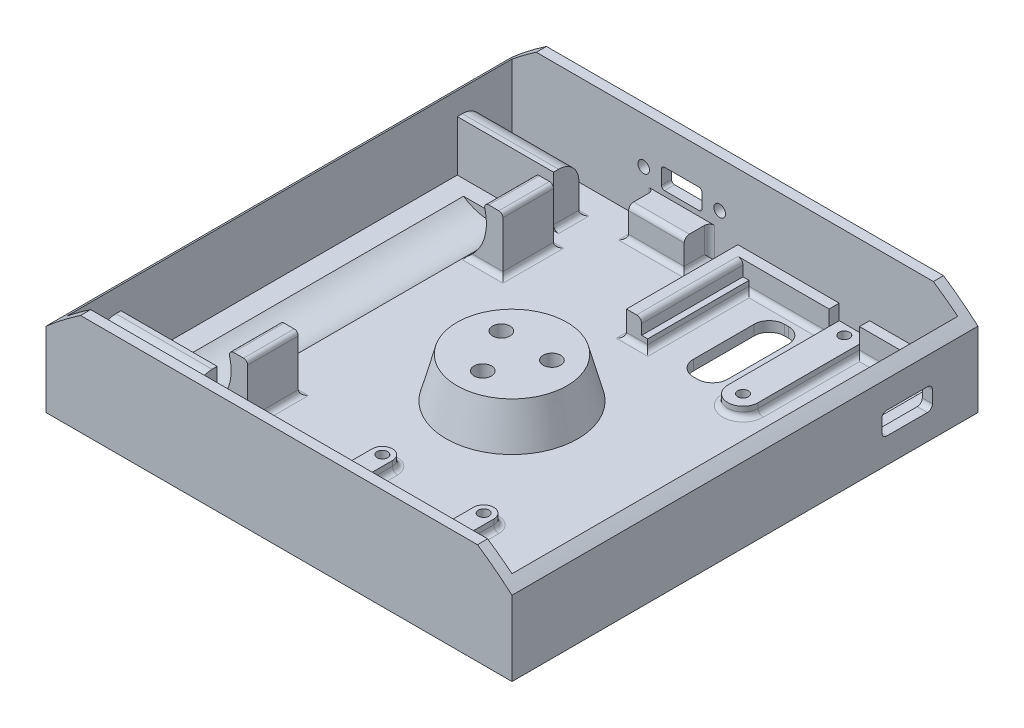
SolidWorks part; units mm, degrees
ref_plane "Front Plane" through (0, 0, 0) normal (0, 0, 1) x (1, 0, 0)
ref_plane "Top Plane" through (0, 0, 0) normal (0, 1, 0) x (1, 0, 0)
ref_plane "Right Plane" through (0, 0, 0) normal (1, 0, 0) x (0, 0, -1)
sketch "Sketch1" plane through (0, 0, 0) normal (0, 1, 0) x (1, 0, 0)
  line L1 (-46, 46) -> (46, 46)
  line L2 (-46, 46) -> (-46, -46)
  line L3 (-46, -46) -> (46, -46)
  line L4 (46, 46) -> (46, -46)
  line L5 (-46, 46) -> (46, -46) construction
  line L6 (-46, -46) -> (46, 46) construction
  point P0 (0, 0)
  dimension "D1" = 92
  dimension "D2" = 92
extrude "Boss-Extrude1" add sketch "Sketch1" along normal blind 2
sketch "Sketch7" plane through (0, 2, 0) normal (0, 1, 0) x (1, 0, 0)
  circle A0 centre (0, 0) radius 13
  dimension "D1" = 26
extrude "Boss-Extrude2" add sketch "Sketch7" along normal blind 8 draft 15
sketch "Sketch4" plane through (0, 2, 0) normal (0, 1, 0) x (1, 0, 0)
  circle A3 centre (0, -5.77) radius 1.725
  circle A4 centre (-4.997, 2.885) radius 1.725
  circle A5 centre (4.997, 2.885) radius 1.725
  point P10 (0, 0)
  dimension "D2" = 3.45
  dimension "D1" = 5.77
  dimension "D3" = 3
extrude "Cut-Extrude3" cut sketch "Sketch4" against normal through all both and the other way through all
sketch "Sketch6" plane through (0, 2, 0) normal (0, 1, 0) x (1, 0, 0)
  circle A3 centre (0, -5.77) radius 3.5
  circle A4 centre (4.997, 2.885) radius 3.5
  circle A5 centre (-4.997, 2.885) radius 3.5
  dimension "D1" = 7
  dimension "D2" = 7
  dimension "D3" = 7
extrude "Cut-Extrude4" cut sketch "Sketch6" against normal through all from offset 1
sketch "Sketch8" plane through (0, 2, 0) normal (0, 1, 0) x (1, 0, 0)
  line L0 (-46, 0) -> (46, 0) construction
  line L1 (-46, 46) -> (-46, -46) construction
  line L2 (46, -46) -> (46, 46) construction
  line L3 (-44, -33.2) -> (-25, -33.2)
  line L4 (-44, 38.2) -> (-25, 38.2)
  line L5 (-44, 38.2) -> (-44, 33.2)
  line L6 (-44, 33.2) -> (-25, 33.2)
  line L7 (-25, 38.2) -> (-25, 33.2)
  line L8 (-44, 38.2) -> (-25, 33.2) construction
  line L9 (-44, 33.2) -> (-25, 38.2) construction
  line L10 (-25, -38.2) -> (-25, -33.2)
  line L11 (-44, -38.2) -> (-44, -33.2)
  line L12 (-44, -38.2) -> (-25, -38.2)
  circle A0 centre (0, 0) radius 25 construction
  point P9 (-34.5, 35.7)
  dimension "D1" = 50
  dimension "D2" = 19
  dimension "D3" = 25
  dimension "D4" = 5
  dimension "D5" = 33.2
extrude "Boss-Extrude3" add sketch "Sketch8" along normal blind 10
fillet "Fillet1" radius 4 2 edges at (-34.5, 12, -38.2) (-34.5, 12, 38.2)
sketch "Sketch12" plane through (0, 2, 0) normal (0, 1, 0) x (1, 0, 0)
  line L0 (-46, 0) -> (46, 0) construction
  line L5 (-46, 46) -> (-46, -46) construction
  line L6 (46, -46) -> (46, 46) construction
  line L12 (-25, 33.2) -> (-25, 38.2) construction
  line L13 (-29, 30.2) -> (-22, 30.2)
  line L14 (-29, 30.2) -> (-29, 20.2)
  line L15 (-29, 20.2) -> (-22, 20.2)
  line L16 (-22, 30.2) -> (-22, 20.2)
  line L17 (-44, 33.2) -> (-25, 33.2) construction
  line L18 (-29, -20.2) -> (-22, -20.2)
  line L19 (-22, -30.2) -> (-22, -20.2)
  line L20 (-29, -30.2) -> (-29, -20.2)
  line L21 (-29, -30.2) -> (-22, -30.2)
  dimension "D1" = 10
  dimension "D2" = 7
  dimension "D3" = 4
  dimension "D4" = 3
extrude "Boss-Extrude6" add sketch "Sketch12" along normal blind 11
sketch "Sketch16" plane through (0, 0, 30.2) normal (0, 0, 1) x (1, 0, 0)
  line L0 (-46, 2) -> (46, 2) construction
  line L1 (-25, 8) -> (-25, 2) construction
  circle A0 centre (-34.5, 9.6) radius 9.25
  dimension "D1" = 18.5
  dimension "D2" = 7.6
  dimension "D3" = 9.5
extrude "Cut-Extrude5" cut sketch "Sketch16" against normal up to surface (60.4 mm away) up to face at (-25.5, 7.5, -30.2)
fillet "Fillet3" radius 0.8 6 edges at (-25.8975, 13, -25.2) (-22, 13, -25.2) (-22, 13, 25.2) (-25.8975, 13, 25.2) (-29, 2.1628, 25.2) (-29, 2.1628, -25.2)
sketch "Sketch17" plane through (0, 2, 0) normal (0, 1, 0) x (1, 0, 0)
  line L0 (-44, 44) -> (44, 44)
  line L1 (-46, 46) -> (46, 46)
  line L2 (-46, 46) -> (-46, -46)
  line L3 (-46, -46) -> (46, -46)
  line L4 (46, 46) -> (46, -46)
  line L5 (44, 44) -> (44, -44)
  line L6 (-44, -44) -> (44, -44)
  line L7 (-44, 44) -> (-44, -44)
  dimension "D1" = 2
extrude "Boss-Extrude11" add sketch "Sketch17" along normal blind 18
sketch "Sketch19" plane through (0, 0, 46) normal (0, 0, 1) x (1, 0, 0)
  line L0 (-46, 0) -> (46, 0) construction
  circle A1 centre (0, -38) radius 70
  circle A2 centre (0, -38) radius 100
  dimension "D1" = 38
  dimension "D2" = 140
  dimension "D3" = 30
extrude "Cut-Extrude6" cut sketch "Sketch19" against normal up to surface (92 mm away) up to face at (0, 10, -46)
sketch "Sketch20" plane through (0, 2, 0) normal (0, 1, 0) x (1, 0, 0)
  line L0 (0.6, 44) -> (0.6, 22)
  line L1 (44, 44) -> (26.6, 44)
  line L2 (44, 44) -> (44, 42)
  line L3 (44, 42) -> (26.6, 42)
  line L7 (0.6, 22) -> (3.6, 22)
  line L8 (3.6, 42) -> (3.6, 22)
  line L9 (26.6, 44) -> (26.6, 42)
  line L10 (20.6, 44) -> (20.6, 42)
  line L11 (20.6, 44) -> (0.6, 44)
  line L12 (20.6, 42) -> (3.6, 42)
  dimension "D1" = 2
  dimension "D2" = 17.4
  dimension "D3" = 3
  dimension "D4" = 20
  dimension "D5" = 17
  dimension "D6" = 6
extrude "Boss-Extrude12" add sketch "Sketch20" along normal blind 5
sketch "Sketch21" plane through (0, 2, 0) normal (0, 1, 0) x (1, 0, 0)
  line L0 (3.6, 42) -> (20.6, 42) construction
  line L1 (26.6, 44) -> (20.6, 44)
  line L2 (26.6, 44) -> (26.6, 22)
  line L4 (20.6, 44) -> (20.6, 22)
  line L5 (44, 42) -> (41, 42)
  line L6 (44, 42) -> (44, 22)
  line L7 (44, 22) -> (41, 22)
  line L8 (41, 42) -> (41, 22)
  line L9 (3.6, 42) -> (4.8, 42)
  line L10 (3.6, 42) -> (3.6, 22)
  line L11 (3.6, 22) -> (4.8, 22)
  line L12 (4.8, 42) -> (4.8, 22)
  arc A0 (20.6, 22) -> (26.6, 22) centre (23.6, 22) ccw
  dimension "D7" = 3
  dimension "D1" = 1.2
  dimension "D2" = 20
  dimension "D4" = 20
  dimension "D5" = 3
  dimension "D6" = 20
  dimension "D8" = 6
extrude "Boss-Extrude13" add sketch "Sketch21" along normal blind 2
sketch "Sketch22" plane through (0, 4, 0) normal (0, 1, 0) x (1, 0, 0)
  line L0 (20.6, 42) -> (20.6, 22) construction
  circle A0 centre (23.6, 22) radius 1.05
  circle A1 centre (23.6, 42) radius 1.05
  dimension "D1" = 2.1
  dimension "D2" = 2.1
  dimension "D3" = 3
extrude "Cut-Extrude7" cut sketch "Sketch22" against normal through all
sketch "Sketch23" plane through (44, 0, 0) normal (-1, 0, 0) x (0, 0, 1)
  line L0 (-22, 4) -> (-42, 4) construction
  line L1 (-36, 9.4) -> (-28, 9.4)
  line L2 (-37, 8.4) -> (-37, 6)
  line L3 (-36, 5) -> (-28, 5)
  line L4 (-27, 8.4) -> (-27, 6)
  line L5 (-42, 7) -> (-42, 4) construction
  arc A0 (-36, 5) -> (-37, 6) centre (-36, 6) cw
  arc A1 (-28, 5) -> (-27, 6) centre (-28, 6) ccw
  arc A2 (-28, 9.4) -> (-27, 8.4) centre (-28, 8.4) cw
  arc A3 (-36, 9.4) -> (-37, 8.4) centre (-36, 8.4) ccw
  point P12 (-27, 5)
  point P15 (-27, 9.4)
  point P18 (-37, 9.4)
  dimension "D5" = 1
  dimension "D1" = 1
  dimension "D2" = 4.4
  dimension "D3" = 10
  dimension "D4" = 5
extrude "Cut-Extrude8" cut sketch "Sketch23" against normal through all
sketch "Sketch24" plane through (0, 2, 0) normal (0, 1, 0) x (1, 0, 0)
  line L0 (-44, -44) -> (44, -44) construction
  line L1 (16.4, -44) -> (20.4, -44)
  line L2 (16.4, -44) -> (16.4, -24)
  line L4 (20.4, -44) -> (20.4, -24)
  line L5 (44, -44) -> (44, 22) construction
  line L6 (-3.6, -44) -> (0.4, -44)
  line L7 (-3.6, -44) -> (-3.6, -24)
  line L9 (0.4, -44) -> (0.4, -24)
  line L10 (-22, -30.2) -> (-22, -20.2) construction
  line L11 (44, 6.5) -> (37, 6.5)
  line L12 (44, 6.5) -> (44, -0.5)
  line L13 (44, -0.5) -> (37, -0.5)
  arc A0 (0.4, -24) -> (-3.6, -24) centre (-1.6, -24) ccw
  arc A1 (20.4, -24) -> (16.4, -24) centre (18.4, -24) ccw
  arc A2 (37, 6.5) -> (37, -0.5) centre (37, 3) ccw
  circle A4 centre (23.6, 22) radius 1.05 construction
  dimension "D1" = 20
  dimension "D2" = 20
  dimension "D3" = 4
  dimension "D4" = 4
  dimension "D5" = 18.4
  dimension "D6" = 16
  dimension "D7" = 7
  dimension "D8" = 7
  dimension "D9" = 15.5
extrude "Boss-Extrude14" add sketch "Sketch24" along normal blind 2
sketch "Sketch25" plane through (0, 4, 0) normal (0, 1, 0) x (1, 0, 0)
  circle A0 centre (-1.6, -24) radius 1.05
  circle A1 centre (18.4, -24) radius 1.05
  circle A2 centre (37, 3) radius 1.05
  dimension "D1" = 2.1
  dimension "D2" = 2.1
  dimension "D3" = 2.1
extrude "Cut-Extrude9" cut sketch "Sketch25" against normal through all
sketch "Sketch27" plane through (0, 2, 0) normal (0, 1, 0) x (1, 0, 0)
  line L0 (0.6, 44) -> (-44, 44) construction
  line L1 (-16, 44) -> (-5, 44)
  line L2 (-16, 44) -> (-16, 39)
  line L3 (-16, 39) -> (-5, 39)
  line L4 (-5, 44) -> (-5, 39)
  line L6 (-46, 46) -> (-46, -46) construction
  dimension "D1" = 5
  dimension "D2" = 11
  dimension "D3" = 30
extrude "Boss-Extrude15" add sketch "Sketch27" along normal blind 6
sketch "Sketch28" plane through (0, 0, -44) normal (0, 0, 1) x (1, 0, 0)
  line L0 (-5, 8) -> (-16, 8) construction
  line L1 (-13.9, 13) -> (-7.1, 13)
  line L2 (-14.5, 12.4) -> (-14.5, 9.6)
  line L3 (-13.9, 9) -> (-7.1, 9)
  line L4 (-6.5, 12.4) -> (-6.5, 9.6)
  circle A0 centre (-18, 11) radius 1.15
  circle A1 centre (-3, 11) radius 1.15
  arc A2 (-6.5, 12.4) -> (-7.1, 13) centre (-7.1, 12.4) ccw
  arc A3 (-7.1, 9) -> (-6.5, 9.6) centre (-7.1, 9.6) ccw
  arc A4 (-13.9, 9) -> (-14.5, 9.6) centre (-13.9, 9.6) cw
  arc A5 (-14.5, 12.4) -> (-13.9, 13) centre (-13.9, 12.4) cw
  point P13 (-6.5, 13)
  point P18 (-14.5, 9)
  point P21 (-14.5, 13)
  dimension "D9" = 2.3
  dimension "D10" = 2.3
  dimension "D11" = 0.6
  dimension "D1" = 8
  dimension "D2" = 1.5
  dimension "D3" = 4
  dimension "D4" = 1
  dimension "D5" = 2
  dimension "D6" = 2
  dimension "D7" = 3.5
  dimension "D8" = 3.5
extrude "Cut-Extrude10" cut sketch "Sketch28" against normal through all
fillet "Fillet4" radius 1 1 edges at (3.6, 7, -32)
fillet "Fillet5" radius 1 6 edges at (-16, 5, -44) (-5, 5, -44) (-5, 2, -41.5) (-16, 2, -41.5) (-10.5, 2, -39) (-10.5, 8, -39)
fillet "Fillet6" radius 1 29 edges at (26.6, 2, -32) (23.6, 2, -19) (12.7, 2, -42) (33.8, 2, -42) (42.5, 2, -22) (41, 2, -32) (20.6, 2, -32) (4.8, 2, -32) (2.7, 2, -22) (0.6, 2, -33) (40.5, 2, -6.5) (33.5, 2, -3) (16.4, 2, 34) (18.4, 2, 22) (-3.6, 2, 34) (-1.6, 2, 22) (40.5, 2, 0.5) (20.4, 2, 34) (0.4, 2, 34) (-34.5, 2, 38.2) (-25, 2, 35.7) (-25.5, 2, 30.2) (-25.5, 2, 20.2) (-22, 2, 25.2) (-34.5, 2, -38.2) (-25, 2, -35.7) (-25.5, 2, -30.2) (-25.5, 2, -20.2) (-22, 2, -25.2)
sketch "Sketch29" plane through (0, 2, 0) normal (0, 1, 0) x (1, 0, 0)
  line L0 (39.1918, 44) -> (-39.1918, 44) construction
  line L1 (10.8, 40) -> (17.6, 40)
  line L2 (10.8, 40) -> (10.8, 22)
  line L3 (10.8, 22) -> (17.6, 22)
  line L4 (17.6, 40) -> (17.6, 22)
  line L5 (29.6, 40) -> (37, 40)
  line L6 (29.6, 40) -> (29.6, 22)
  line L7 (29.6, 22) -> (37, 22)
  line L8 (37, 40) -> (37, 22)
  line L9 (44, 44) -> (26.6, 44) construction
  line L10 (5.8, 41) -> (5.8, 21) construction
  line L11 (19.6, 22) -> (19.6, 41) construction
  line L12 (27.6, 41) -> (27.6, 22) construction
  line L13 (40, 21) -> (40, 41) construction
  dimension "D1" = 4
  dimension "D2" = 4
  dimension "D3" = 5
  dimension "D4" = 2
  dimension "D5" = 2
  dimension "D6" = 3
  dimension "D7" = 18
  dimension "D8" = 18
extrude "Cut-Extrude11" cut sketch "Sketch29" against normal through all
fillet "Fillet7" radius 3 8 edges at (29.6, 1, -22) (10.8, 1, -22) (17.6, 1, -22) (37, 1, -22) (29.6, 1, -40) (37, 1, -40) (17.6, 1, -40) (10.8, 1, -40)
